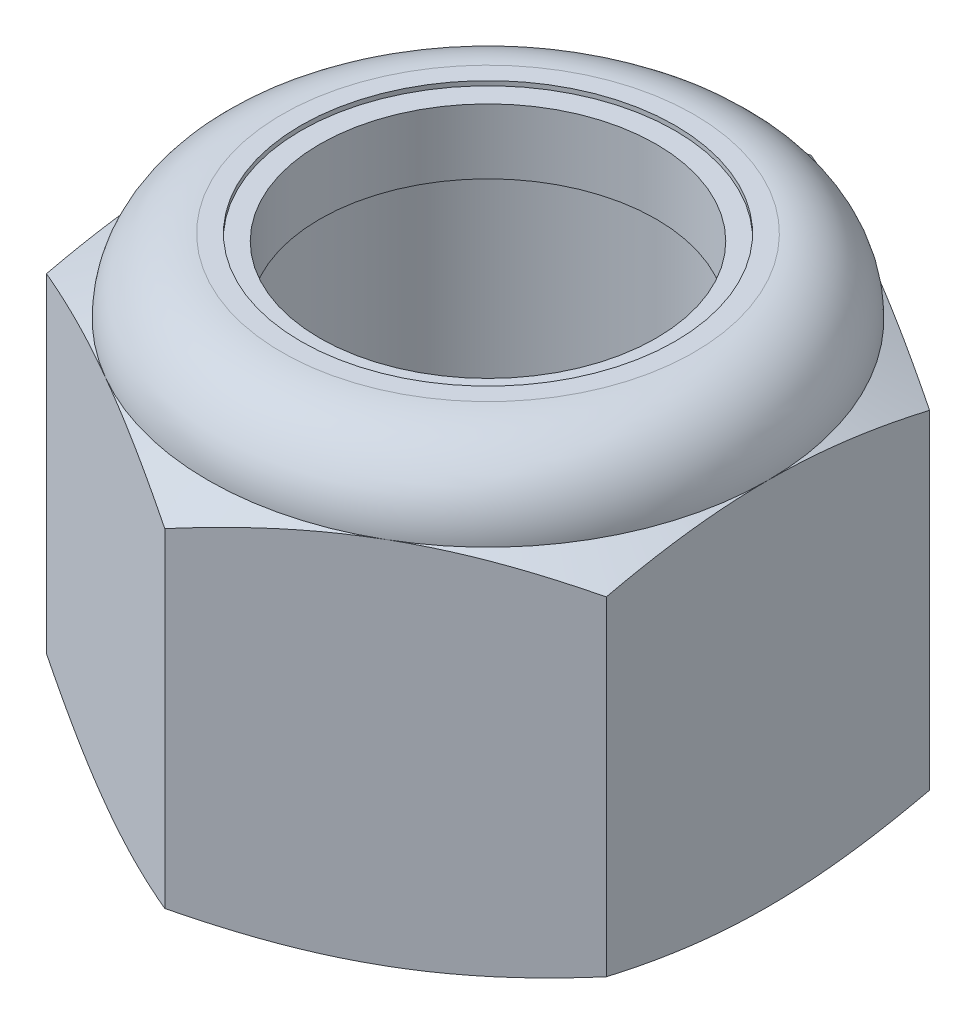
SolidWorks part; units mm, degrees
material "Plain Carbon Steel"
ref_plane "Front" through (0, 0, 0) normal (0, 0, 1) x (1, 0, 0)
ref_plane "Top" through (0, 0, 0) normal (0, 1, 0) x (1, 0, 0)
ref_plane "Right" through (0, 0, 0) normal (1, 0, 0) x (0, 0, -1)
sketch "Sketch1" plane through (0, 0, 0) normal (0, 1, 0) x (1, 0, 0)
  line L1 (0, 10.9985) -> (-9.525, 5.4993)
  line L2 (-9.525, 5.4993) -> (-9.525, -5.4993)
  line L3 (-9.525, -5.4993) -> (0, -10.9985)
  line L4 (0, -10.9985) -> (9.525, -5.4993)
  line L5 (9.525, -5.4993) -> (9.525, 5.4993)
  line L6 (9.525, 5.4993) -> (0, 10.9985)
  circle A0 centre (0, 0) radius 9.525 construction
  dimension "Hex Flats" = 19.05
extrude "Extrude1" add sketch "Sketch1" along normal blind 15.0812
sketch "Sketch2" plane through (0, 0, 0) normal (1, 0, 0) x (0, 0, -1)
  line L0 (-6.35, 0) -> (-6.35, 15.0812) construction
  line L1 (0, 0) -> (6.35, 0)
  line L2 (0, 0) -> (0, 15.0812)
  line L3 (0, 15.0812) -> (6.35, 15.0812)
  line L4 (6.35, 0) -> (6.35, 15.0812)
  line L5 (-5.4993, 15.0812) -> (5.4993, 15.0812) construction
  line L7 (0, -6.35) -> (0, 0) construction
  dimension "Thread Dia" = 12.7
revolve "Revolve1" add sketch "Sketch2" angle 360 about L7
sketch "Sketch3" plane through (0, 0, 0) normal (1, 0, 0) x (0, 0, -1)
  line L0 (6.35, 15.0813) -> (-6.35, 15.0812) construction
  line L1 (-6.35, 15.0812) -> (-6.35, 13.8113) construction
  line L2 (-6.35, 13.8113) -> (6.35, 15.0813) construction
  line L3 (6.35, 15.0813) -> (6.3658, 14.9233) construction
  line L4 (6.3658, 14.9233) -> (6.4764, 13.8176)
  line L5 (6.4764, 13.8176) -> (5.7529, 14.1441)
  line L6 (5.7529, 14.1441) -> (5.7213, 14.46)
  line L7 (5.7213, 14.46) -> (6.3658, 14.9233)
  line L8 (5.7371, 14.302) -> (6.4211, 14.3704) construction
  line L9 (6.35, 15.0813) -> (6.35, 14.3633) construction
  line L10 (6.35, 14.3633) -> (-6.35, 13.0933) construction
  line L11 (-6.35, 13.0933) -> (-6.35, 13.8113) construction
  line L12 (-0.1353, 15.0813) -> (0.1353, 12.3754) construction
  line L13 (-6.35, 0) -> (-6.35, 15.0812) construction
  line L14 (0, 15.0812) -> (6.35, 15.0812) construction
  line L15 (6.35, 0) -> (6.35, 15.0812) construction
  point P13 (0, 13.7283)
  dimension "D1" = 0.1588
  dimension "D2" = 0.3175
  dimension "Thread Pitch" = 1.27
  dimension "D4" = 60
  dimension "D5" = 1.27
revolve "Cut-Revolve1" [suppressed] cut sketch "Sketch3" angle 360 about L12
pattern_linear "LPattern1" [suppressed] count 12 spacing 1.27 along (0, -1, 0) count 2 spacing 1.27 along (0, 1, 0) of bodies 110
sketch "Sketch4" plane through (0, 0, 0) normal (1, 0, 0) x (0, 0, -1)
  line L0 (0, 15.0812) -> (6.35, 15.0812)
  line L1 (6.35, 15.0812) -> (5.7213, 14.7881)
  line L2 (5.7213, 14.7881) -> (5.7213, 0.2932)
  line L3 (5.7213, 0.2932) -> (6.35, 0)
  line L4 (6.35, 0) -> (0, 0)
  line L5 (0, 0) -> (0, 15.0812)
  line L6 (6.35, 0) -> (6.35, 15.0812) construction
  line L7 (0, 15.0812) -> (6.35, 15.0812) construction
  line L8 (0, 0) -> (6.35, 0) construction
  line L9 (0, 0) -> (0, 15.0812) construction
  line L10 (0, 15.0812) -> (0, 15.775) construction
  dimension "D1" = 25
revolve "Cut-Revolve2" cut sketch "Sketch4" angle 360 about L10
combine bodies "Combine1" operation type subtract main body 112 bodies to subtract 109
sketch "Sketch5" plane through (0, 0, 0) normal (1, 0, 0) x (0, 0, -1)
  line L0 (0, 0) -> (9.525, 0)
  line L1 (9.525, 0) -> (10.9985, 0.6871)
  line L2 (10.9985, 0.6871) -> (10.9985, 11.8806)
  line L3 (10.9985, 11.8806) -> (9.525, 12.5677)
  line L4 (7.0115, 15.0813) -> (7.0115, 16.3513)
  line L5 (7.0115, 16.3513) -> (12.2685, 16.3513)
  line L6 (12.2685, 16.3513) -> (12.2685, -1.27)
  line L7 (12.2685, -1.27) -> (0, -1.27)
  line L8 (0, -1.27) -> (0, 0)
  line L9 (9.525, 12.5677) -> (9.525, 0) construction
  line L10 (0, 0) -> (6.35, 0) construction
  line L13 (10.9985, 6.2839) -> (12.2685, 6.2839) construction
  line L14 (10.9985, 15.0812) -> (10.9985, 0) construction
  line L15 (0, 0) -> (0, 16.3513) construction
  line L20 (0, 16.3513) -> (7.0115, 16.3513) construction
  line L22 (0, 15.0812) -> (6.35, 15.0812) construction
  arc A0 (9.525, 12.5677) -> (7.0115, 15.0813) centre (7.0115, 12.5677) ccw
  dimension "D1" = 25
  dimension "D2" = 1.27
  dimension "D3" = 15.0813
  dimension "D4" = 2.5135
revolve "Cut-Revolve3" cut sketch "Sketch5" angle 360 about L15
sketch "Sketch6" plane through (0, 0, 0) normal (1, 0, 0) x (0, 0, -1)
  line L0 (0, 12.5677) -> (9.3726, 12.5677)
  line L1 (7.0115, 14.9289) -> (6.3664, 14.9289)
  line L2 (0, 16.3513) -> (0, 12.5677)
  line L3 (6.3664, 16.3513) -> (0, 16.3513)
  line L4 (0, 16.3513) -> (7.0115, 16.3513) construction
  line L5 (0, 0) -> (0, 16.3513) construction
  line L6 (0, 16.3513) -> (0, 44.323) construction
  line L7 (6.3664, 14.9289) -> (6.3664, 16.3513)
  line L8 (7.0115, 15.0813) -> (7.0115, 14.9289) construction
  line L9 (6.3664, 14.9289) -> (5.7213, 14.9289) construction
  line L10 (5.7213, 14.9289) -> (5.7213, 14.7881) construction
  arc A0 (9.3726, 12.5677) -> (7.0115, 14.9289) centre (7.0115, 12.5677) ccw
  arc A1 (9.525, 12.5677) -> (7.0115, 15.0813) centre (7.0115, 12.5677) ccw construction
  dimension "D1" = 0.1524
revolve "Cut-Revolve4" cut sketch "Sketch6" angle 360 about L6
sketch "Sketch7" plane through (0, 0, 0) normal (1, 0, 0) x (0, 0, -1)
  line L0 (5.7213, 12.6439) -> (9.2951, 12.6439)
  line L1 (7.0115, 14.8527) -> (5.7213, 14.8527)
  line L2 (5.7213, 14.8527) -> (5.7213, 12.6439)
  line L3 (5.7213, 12.6439) -> (0, 12.6439) construction
  line L4 (0, 12.6439) -> (0, 14.8527) construction
  line L5 (0, 14.8527) -> (5.7213, 14.8527) construction
  line L6 (5.7213, 12.6439) -> (5.7213, 12.5677) construction
  line L7 (0, 12.5677) -> (9.3726, 12.5677) construction
  line L8 (7.0115, 14.8527) -> (7.0115, 14.9289) construction
  arc A0 (9.2951, 12.6439) -> (7.0115, 14.8527) centre (7.0115, 12.5677) ccw
  arc A2 (9.3726, 12.5677) -> (7.0115, 14.9289) centre (7.0115, 12.5677) ccw construction
  dimension "D1" = 0.0762
revolve "Revolve2" add sketch "Sketch7" angle 360 about L4
equation "\"D1@Sketch3\"=\"Thread Pitch@Sketch3\"/8"
equation "\"D2@Sketch3\"=\"Thread Pitch@Sketch3\"/4"
equation "\"D5@Sketch3\"=\"Thread Pitch@Sketch3\""
equation "\"D4@LPattern1\"=\"Thread Pitch@Sketch3\""
equation "\"D3@LPattern1\"=\"Thread Pitch@Sketch3\""
equation "\"D1@LPattern1\"=\"Height@Extrude1\"/\"Thread Pitch@Sketch3\""
equation "\"D4@Sketch5\"=\"Height@Extrude1\"/6"
